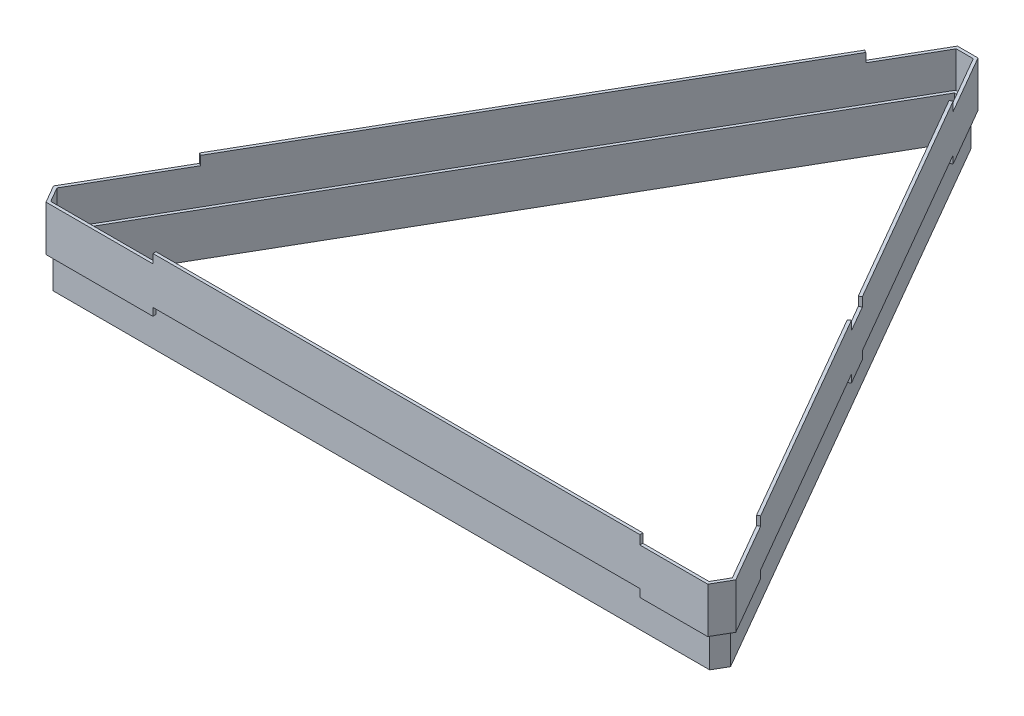
SolidWorks part; units mm, degrees
ref_plane "Front Plane" through (0, 0, 0) normal (0, 0, 1) x (1, 0, 0)
ref_plane "Top Plane" through (0, 0, 0) normal (0, 1, 0) x (1, 0, 0)
ref_plane "Right Plane" through (0, 0, 0) normal (1, 0, 0) x (0, 0, -1)
sketch "Sketch1" plane through (0, 0, 0) normal (0, 1, 0) x (1, 0, 0)
  line L17 (-4, 192.2576) -> (111, -6.9282) construction
  line L24 (4, 192.2576) -> (-111, -6.9282) construction
  line L25 (-115, 0) -> (115, 0) construction
  line L26 (-96.004, 30.9021) -> (-95.1379, 30.4021)
  line L27 (-111.2679, -2.4641) -> (-110.8349, -2.2141) construction
  line L28 (0, 192.2576) -> (0, 185.3294) construction
  line L29 (113, -3.4641) -> (107, 0) construction
  line L30 (59.5, 96.1288) -> (57.7679, 95.1288) construction
  line L31 (-59.5, 96.1288) -> (-57.7679, 95.1288) construction
  line L33 (-112.6906, 0) -> (-109.8453, -4.9282)
  line L36 (112.6906, 0) -> (109.8453, -4.9282)
  line L37 (-2.8453, 190.2576) -> (2.8453, 190.2576)
  line L46 (-74.74, -4.9282) -> (87.75, -4.9282)
  line L50 (-112.6906, 0) -> (-95.1379, 30.4021)
  line L51 (-13.8929, 171.1225) -> (-95.1379, 30.4021)
  line L52 (-14.759, 171.6225) -> (-13.8929, 171.1225)
  line L53 (-14.759, 171.6225) -> (-96.004, 30.9021)
  line L54 (13.8929, 171.1225) -> (14.759, 171.6225)
  line L55 (-109.8453, -4.9282) -> (-74.74, -4.9282)
  line L56 (109.8453, -4.9282) -> (87.75, -4.9282)
  line L57 (-74.74, -5.9282) -> (-74.74, -4.9282)
  line L58 (61.134, 91.2987) -> (56.134, 99.9589)
  line L59 (-2.8453, 190.2576) -> (-13.8929, 171.1225)
  line L60 (61.134, 91.2987) -> (102.509, 19.6351)
  line L61 (102.509, 19.6351) -> (113.8453, 0)
  line L62 (101.6429, 19.1351) -> (102.509, 19.6351)
  line L63 (101.6429, 19.1351) -> (112.6906, 0)
  line L64 (2.8453, 190.2576) -> (13.8929, 171.1225)
  line L65 (113.8453, 0) -> (110.4226, -5.9282)
  line L66 (56.134, 99.9589) -> (14.759, 171.6225)
  line L67 (55.2679, 99.4589) -> (13.8929, 171.1225)
  line L68 (0, -6.9282) -> (-74.74, -6.9282) construction
  line L69 (-14.759, 171.6225) -> (-3.4226, 191.2576)
  line L70 (-58.634, 95.6288) -> (-96.004, 30.9021) construction
  line L71 (-3.4226, 191.2576) -> (3.4226, 191.2576)
  line L72 (60.2679, 90.7987) -> (61.134, 91.2987)
  line L73 (55.2679, 99.4589) -> (56.134, 99.9589)
  line L74 (55.2679, 99.4589) -> (60.2679, 90.7987)
  line L75 (-74.74, -5.9282) -> (87.75, -5.9282)
  line L76 (60.2679, 90.7987) -> (101.6429, 19.1351)
  line L77 (57.7679, 95.1288) -> (57.3349, 94.8788) construction
  line L78 (57.3349, 94.8788) -> (-110.8349, -2.2141) construction
  line L79 (-110.8349, -2.2141) -> (-112.1132, 0)
  line L80 (-112.1132, 0) -> (-2.5566, 189.7576)
  line L81 (-2.5566, 189.7576) -> (2.5566, 189.7576)
  line L82 (2.5566, 189.7576) -> (112.1132, 0)
  line L83 (112.1132, 0) -> (109.5566, -4.4282)
  line L84 (109.5566, -4.4282) -> (-109.5566, -4.4282)
  line L85 (-109.5566, -4.4282) -> (-110.8349, -2.2141)
  line L86 (-57.3349, 94.8788) -> (-56.4689, 94.3788) construction
  line L93 (-56.4689, 94.3788) -> (-1.9793, 188.7576)
  line L94 (-1.9793, 188.7576) -> (1.9793, 188.7576)
  line L95 (1.9793, 188.7576) -> (110.9585, 0)
  line L96 (110.9585, 0) -> (108.9793, -3.4282)
  line L97 (108.9793, -3.4282) -> (-108.9793, -3.4282)
  line L98 (-108.9793, -3.4282) -> (-110.9585, 0)
  line L99 (-110.9585, 0) -> (-56.4689, 94.3788)
  line L100 (-111.2679, -2.4641) -> (-112.134, -2.9641) construction
  line L101 (-112.134, -2.9641) -> (-113.8453, 0)
  line L102 (-113.8453, 0) -> (-96.004, 30.9021)
  line L103 (-112.134, -2.9641) -> (-110.4226, -5.9282)
  line L104 (-110.4226, -5.9282) -> (-74.74, -5.9282)
  line L105 (3.4226, 191.2576) -> (14.759, 171.6225)
  line L106 (110.4226, -5.9282) -> (87.75, -5.9282)
  line L107 (87.75, -5.9282) -> (87.75, -4.9282)
  point P23 (-57.7679, 95.1288)
  point P28 (57.7679, 95.1288)
  point P29 (58.634, 95.6288)
  point P34 (-58.634, 95.6288)
  point P38 (14.759, 171.6225)
  point P41 (-14.759, 171.6225)
  point P44 (102.509, 19.6351)
  point P47 (-96.004, 30.9021)
  point P48 (59.5, 96.1288)
  point P62 (-54.7369, 93.3788)
  dimension "D1" = 8
  dimension "D2" = 8
  dimension "D3" = 8
  dimension "D4" = 230
  dimension "D5" = 230
  dimension "D6" = 230
  dimension "D7" = 74.74
  dimension "D8" = 2
extrude "Boss-Extrude1" add sketch "Sketch1" along normal blind 0.2 contours L59 L37 L64 | L76 L74 L67 L64 L37 L59 L51 L50 L33 L55 L46 L56 L36 L63 L84 L85 L79 L80 L81 L82 L83 | L67 | L74 | L76 | L63 L36 L56 | L46 | L55 L33 L50 | L51 | L85 L84 L83 L82 L81 L80 L79 region at (-54.9485, 0, -101.0123) region at (-95.8396, 0, -30.1869) region at (-54.2572, 0, -100.6132) region at (-8.7814, 0, -181.2614) region at (6.505, 0, 5.4282) region at (35.0135, 0, -135.5407) region at (98.7976, 0, 5.2935) region at (58.201, 0, -95.3788) region at (81.3885, 0, -55.2169) region at (-111.2172, 0, 0.9587)
extrude "Boss-Extrude2" add sketch "Sketch1<7>" along normal blind 12.58 contours L63 L36 L56 | L59 L37 L64 | L55 L33 L50 | L74 region at (-95.8396, 0, -30.1869) region at (-8.7814, 0, -181.2614) region at (98.7976, 0, 5.2935) region at (58.201, 0, -95.3788)
sketch "Sketch1<7>" plane through (0, 0, 0) normal (0, 1, 0) x (1, 0, 0) same geometry as "Sketch1"
extrude "Boss-Extrude3" add sketch "Sketch1<8>" along normal blind 15.58 contours L46 | L51 | L76 | L67 region at (-54.9485, 0, -101.0123) region at (6.505, 0, 5.4282) region at (35.0135, 0, -135.5407) region at (81.3885, 0, -55.2169)
sketch "Sketch1<8>" plane through (0, 0, 0) normal (0, 1, 0) x (1, 0, 0) same geometry as "Sketch1"
extrude "Boss-Extrude4" add sketch "Sketch1<9>" against normal blind 13.38 contours L85 L84 L83 L82 L81 L80 L79 region at (-111.2172, 0, 0.9587)
sketch "Sketch1<9>" plane through (0, 0, 0) normal (0, 1, 0) x (1, 0, 0) same geometry as "Sketch1"
extrude "Boss-Extrude5" add sketch "Sketch1<10>" against normal blind 2.58 contours L74 | L105 L71 L69 L52 L59 L37 L64 L54 | L103 L104 L57 L55 L33 L50 L26 L102 L101 | L107 L106 L65 L61 L62 L63 L36 L56 region at (-95.8396, 0, -30.1869) region at (-8.7814, 0, -181.2614) region at (98.7976, 0, 5.2935) region at (58.201, 0, -95.3788)
sketch "Sketch1<10>" plane through (0, 0, 0) normal (0, 1, 0) x (1, 0, 0) same geometry as "Sketch1"
extrude "Boss-Extrude6" add sketch "Sketch1<11>" along normal blind 1 contours L85 L84 L83 L82 L81 L80 L79 L98 L99 L93 L94 L95 L96 L97 region at (-111.2172, 0, 0.9587)
sketch "Sketch1<11>" plane through (0, 0, 0) normal (0, 1, 0) x (1, 0, 0) same geometry as "Sketch1"
